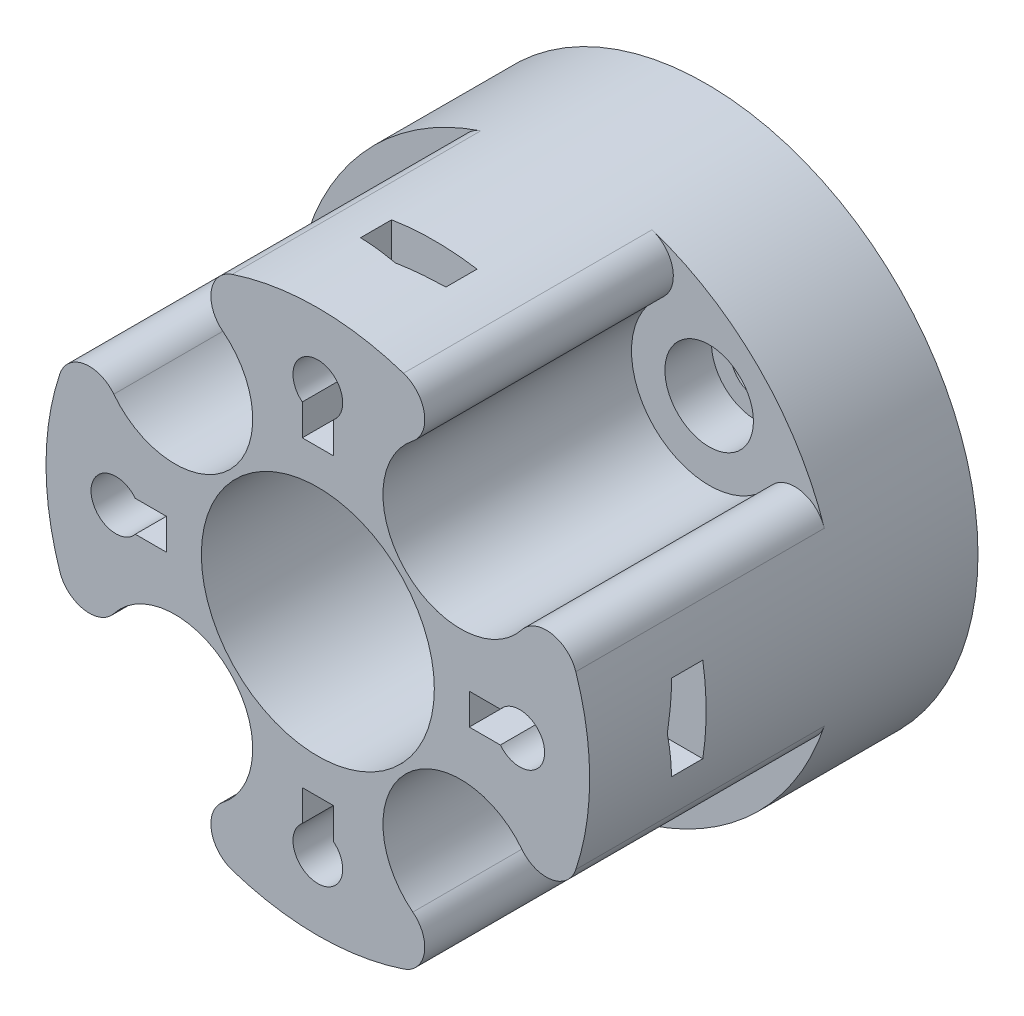
SolidWorks part; units mm, degrees
ref_plane "Front Plane" through (0, 0, 0) normal (1, 0, 0) x (0, 1, 0)
ref_plane "Top Plane" through (0, 0, 0) normal (0, 0, 1) x (0, 1, 0)
ref_plane "Right Plane" through (0, 0, 0) normal (0, 1, 0) x (-1, 0, 0)
sketch "Sketch1" plane through (0, 0, 0) normal (0, 0, 1) x (0, 1, 0)
  line L0 (0, 0) -> (9.1924, 9.1924) construction
  circle A0 centre (0, 0) radius 17.5
  circle A1 centre (0, 0) radius 13 construction
  circle A2 centre (9.1924, 9.1924) radius 1.6
  circle A3 centre (9.1924, 9.1924) radius 2.85
  circle A4 centre (9.1924, -9.1924) radius 2.85
  circle A5 centre (9.1924, -9.1924) radius 1.6
  circle A6 centre (-9.1924, -9.1924) radius 2.85
  circle A7 centre (-9.1924, -9.1924) radius 1.6
  circle A8 centre (-9.1924, 9.1924) radius 2.85
  circle A9 centre (-9.1924, 9.1924) radius 1.6
  point P19 (0, 0)
  dimension "D1" = 35
  dimension "D2" = 26
  dimension "D3" = 3.2
  dimension "D4" = 5.7
  dimension "D5" = 4
extrude "Boss-Extrude1" add sketch "Sketch1" along normal blind 25 contours A0 A8 A6 A4 A3 region at (0, 0, 0)
extrude "Boss-Extrude2" add sketch "Sketch1<3>" along normal blind 6 contours A6 A7 | A8 A9 | A4 A5 | A3 A2 region at (-9.1924, 6.423, 0) region at (9.1924, 6.423, 0) region at (9.1924, -11.9618, 0) region at (-9.1924, -11.9618, 0)
sketch "Sketch1<3>" plane through (0, 0, 0) normal (0, 0, 1) x (0, 1, 0) same geometry as "Sketch1"
sketch "Sketch2" plane through (0, 0, 25) normal (0, 0, 1) x (1, 0, 0)
  circle A0 centre (-9.1924, 9.1924) radius 5
  circle A1 centre (9.1924, 9.1924) radius 5
  circle A2 centre (9.1924, -9.1924) radius 5
  circle A3 centre (-9.1924, -9.1924) radius 5
  dimension "D1" = 10
  dimension "D2" = 2
  dimension "D3" = 2
extrude "Cut-Extrude1" cut sketch "Sketch2" against normal offset from surface (16 mm away) 9 up to face at (17.5, 0, 0)
fillet "Fillet1" radius 2 8 edges at (14.0286, 10.4618, 17) (-14.0286, 10.4618, 17) (-10.4618, 14.0286, 17) (10.4618, 14.0286, 17) (14.0286, -10.4618, 17) (10.4618, -14.0286, 17) (-10.4618, -14.0286, 17) (-14.0286, -10.4618, 17)
sketch "Sketch3" plane through (0, 0, 25) normal (0, 0, 1) x (1, 0, 0)
  line L0 (-2.75, 15.75) -> (-2.75, 17.2826)
  line L2 (-2.75, 15.75) -> (-2.75, 10.25)
  line L3 (-2.75, 10.25) -> (2.75, 10.25)
  line L4 (2.75, 15.75) -> (2.75, 10.25)
  line L5 (-2.75, 15.75) -> (2.75, 10.25) construction
  line L6 (-2.75, 10.25) -> (2.75, 15.75) construction
  line L7 (2.75, 15.75) -> (2.75, 17.2826)
  line L8 (15.75, -2.75) -> (10.25, -2.75)
  line L9 (10.25, 2.75) -> (10.25, -2.75)
  line L10 (15.75, 2.75) -> (10.25, 2.75)
  line L11 (15.75, 2.75) -> (17.2826, 2.75)
  line L12 (15.75, -2.75) -> (17.2826, -2.75)
  line L13 (-2.75, -15.75) -> (-2.75, -10.25)
  line L14 (2.75, -10.25) -> (-2.75, -10.25)
  line L15 (2.75, -15.75) -> (2.75, -10.25)
  line L16 (2.75, -15.75) -> (2.75, -17.2826)
  line L17 (-2.75, -15.75) -> (-2.75, -17.2826)
  line L18 (-15.75, 2.75) -> (-10.25, 2.75)
  line L19 (-10.25, -2.75) -> (-10.25, 2.75)
  line L20 (-15.75, -2.75) -> (-10.25, -2.75)
  line L21 (-15.75, -2.75) -> (-17.2826, -2.75)
  line L22 (-15.75, 2.75) -> (-17.2826, 2.75)
  circle A0 centre (0, 0) radius 13 construction
  circle A2 centre (0, 13) radius 1.6
  arc A3 (5.5152, 16.6082) -> (-5.5152, 16.6082) centre (0, 0) ccw construction
  arc A4 (-2.75, 17.2826) -> (2.75, 17.2826) centre (0, 0) cw
  arc A5 (17.2826, 2.75) -> (17.2826, -2.75) centre (0, 0) cw
  circle A6 centre (13, 0) radius 1.6
  arc A7 (2.75, -17.2826) -> (-2.75, -17.2826) centre (0, 0) cw
  circle A8 centre (0, -13) radius 1.6
  arc A9 (-17.2826, -2.75) -> (-17.2826, 2.75) centre (0, 0) cw
  circle A10 centre (-13, 0) radius 1.6
  point P41 (0, 0)
  dimension "D1" = 26
  dimension "D2" = 3.2
  dimension "D3" = 5.5
  dimension "D4" = 5.5
  dimension "D5" = 4
extrude "Cut-Extrude2" cut sketch "Sketch3" against normal blind 2.5 from offset 5 offset against normal yes
extrude "Cut-Extrude3" cut sketch "Sketch3<2>" against normal blind 10 contours A10 | A2 | A6 | A8 region at (0, 13, 25) region at (13, 0, 25) region at (0, -13, 25) region at (-13, 0, 25)
sketch "Sketch3<2>" plane through (0, 0, 25) normal (0, 0, 1) x (1, 0, 0) same geometry as "Sketch3"
chamfer "Chamfer1" distance 2.75 distance2 0.5 8 edges at (-13.7663, -2.75, 20) (-2.75, 13.7663, 20) (2.75, 13.7663, 20) (13.7663, 2.75, 20) (13.7663, -2.75, 20) (2.75, -13.7663, 20) (-2.75, -13.7663, 20) (-13.7663, 2.75, 20) first distance on face at (-14.6, 0, 20) first distance on face at (-1.6, 13, 20) first distance on face at (11.4, 0, 20) first distance on face at (-1.6, -13, 20)
sketch "Sketch4" plane through (0, 0, 25) normal (0, 0, 1) x (1, 0, 0)
  circle A0 centre (0, 0) radius 7.5
  dimension "D1" = 15
extrude "Cut-Extrude4" cut sketch "Sketch4" against normal through all contours A0
sketch "Sketch5" plane through (0, 0, 25) normal (0, 0, 1) x (1, 0, 0)
  line L0 (-2.75, 10.25) -> (2.75, 10.25) construction
  line L1 (-1, 13) -> (1, 13)
  line L2 (-1, 13) -> (-1, 9.75)
  line L3 (-1, 9.75) -> (1, 9.75)
  line L4 (1, 13) -> (1, 9.75)
  line L5 (-2.75, 10.25) -> (2.75, 10.25)
  circle A0 centre (0, 13) radius 1.6 construction
  point P6 (0, 13)
  circle M6 centre (0, 13) radius 1.6
  dimension "D1" = 2
  dimension "D2" = 0.5
extrude "Cut-Extrude5" cut sketch "Sketch5" against normal up to surface (7.5 mm away) contours L5 L2 L3 L4 | L2 L5 L4 M6 region at (0, 10.8848, 25) region at (0, 10, 25) up to face at (-1.6, 13, 17.5)
pattern_circular "CirPattern1" count 4 over 360 about axis through (0, 0, 0) along (0, 0, 1) of "Cut-Extrude5" reverse direction yes
